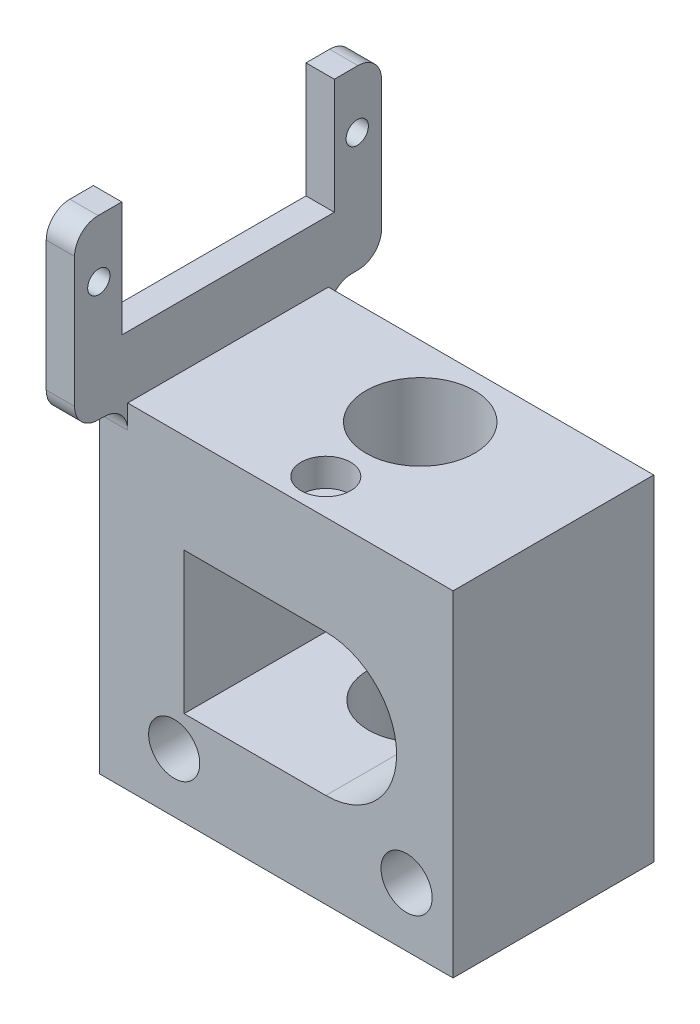
SolidWorks part; units mm, degrees
ref_plane "Front Plane" through (0, 0, 0) normal (0, 0, 1) x (1, 0, 0)
ref_plane "Top Plane" through (0, 0, 0) normal (0, 1, 0) x (1, 0, 0)
ref_plane "Right Plane" through (0, 0, 0) normal (1, 0, 0) x (0, 0, -1)
sketch "Sketch2" plane through (0, 0, 0) normal (0, 0, 1) x (1, 0, 0)
  line L1 (0, 0) -> (35, 0)
  line L2 (0, 0) -> (0, 36.068)
  line L3 (0, 36.068) -> (35, 36.068)
  line L4 (35, 0) -> (35, 36.068)
  dimension "D1" = 36.068
  dimension "D2" = 35
extrude "Boss-Extrude1" add sketch "Sketch2" along normal blind 21.59
hole_wizard "M5 Clearance Hole1" positions "Sketch3" profile "Sketch4" hole size "M5" standard "ANSI Metric" end condition through all
sketch "Sketch3" plane through (0, 0, 0) normal (0, 0, 1) x (1, 0, 0)
  line L0 (5, 6.35) -> (30, 6.35) construction
  line L2 (0, 0) -> (35, 0) construction
  point P0 (5, 6.35)
  point P2 (30, 6.35)
  point P12 (17.5, 0)
  point P13 (17.5, 6.35)
  dimension "D1" = 6.35
  dimension "D2" = 25
sketch "Sketch4" plane through (5, 6.35, 0) normal (1, 0, 0) x (0, 1, 0)
  line L0 (0, 0) -> (0, 21.59)
  line L1 (0, 21.59) -> (2.75, 21.59)
  line L2 (2.75, 21.59) -> (2.75, 0)
  line L5 (2.75, 0) -> (0, 0)
  line L11 (0, -6.35) -> (0, 107.95) construction
  dimension "Thru Hole Dia." = 5.5
  dimension "Thru Hole Depth" = 21.59
sketch "Sketch13" plane through (0, 0, 21.59) normal (0, 0, 1) x (1, 0, 0)
  line L1 (6.07, 25.4) -> (28.93, 25.4)
  line L2 (6.07, 25.4) -> (6.07, 10.16)
  line L3 (6.07, 10.16) -> (28.93, 10.16)
  line L4 (28.93, 25.4) -> (28.93, 10.16)
  line L5 (35, 36.068) -> (0, 36.068) construction
  line L7 (0, 0) -> (35, 0) construction
  point P6 (17.5, 36.068)
  point P7 (17.5, 25.4)
  dimension "D1" = 10.16
  dimension "D2" = 15.24
  dimension "D3" = 22.86
extrude "Cut-Extrude3" cut sketch "Sketch13" against normal through all
sketch "Sketch5" plane through (0, 36.068, 0) normal (0, 1, 0) x (1, 0, 0)
  line L0 (35, 0) -> (0, 0) construction
  circle A0 centre (17.5, -7.62) radius 5.842
  point P6 (17.5, 0)
  dimension "D1" = 11.684
  dimension "D2" = 7.62
extrude "Cut-Extrude1" cut sketch "Sketch5" against normal up to next
sketch "Sketch7" plane through (0, 0, 0) normal (-1, 0, 0) x (0, 0, 1)
  line L0 (21.59, 36.068) -> (0, 36.068) construction
  line L5 (-5.715, 36.068) -> (27.305, 36.068)
  line L6 (-5.715, 36.068) -> (-5.715, 55.118)
  line L7 (-5.715, 55.118) -> (27.305, 55.118)
  line L8 (27.305, 36.068) -> (27.305, 55.118)
  line L9 (21.59, 0) -> (0, 0) construction
  line L10 (-3.1039, 48.9204) -> (24.6939, 48.9204) construction
  line L12 (0, 36.068) -> (21.59, 36.068)
  line L13 (0, 36.068) -> (0, 0)
  line L14 (0, 0) -> (21.59, 0)
  line L15 (21.59, 36.068) -> (21.59, 0)
  line L16 (-0.635, 55.118) -> (22.225, 55.118)
  line L17 (-0.635, 55.118) -> (-0.635, 42.7228)
  line L18 (-0.635, 42.7228) -> (22.225, 42.7228)
  line L19 (22.225, 55.118) -> (22.225, 42.7228)
  point P7 (10.795, 55.118)
  point P10 (10.795, 0)
  point P15 (10.795, 48.9204)
  point P16 (10.795, 36.068)
  point P26 (10.795, 42.7228)
  point P28 (22.225, 48.9204)
  dimension "D1" = 33.02
  dimension "D2" = 19.05
  dimension "D3" = 27.7978
  dimension "D4" = 12.3952
  dimension "D5" = 22.86
extrude "Boss-Extrude2" add sketch "Sketch7" along normal blind 3.048
hole_wizard "M2 Clearance Hole1" positions "Sketch9" profile "Sketch10" hole size "M2" standard "ANSI Metric" end condition through all
sketch "Sketch9" plane through (-3.048, 0, 0) normal (-1, 0, 0) x (0, 0, 1)
  point P0 (-3.1039, 48.9204)
  point P3 (24.6939, 48.9204)
sketch "Sketch10" plane through (-3.048, 48.9204, -3.1039) normal (0, 1, 0) x (0, 0, 1)
  line L0 (0, 0) -> (0, 38.048)
  line L1 (0, 38.048) -> (1.2, 38.048)
  line L2 (1.2, 38.048) -> (1.2, 0)
  line L5 (1.2, 0) -> (0, 0)
  line L11 (0, -6.35) -> (0, 107.95) construction
  dimension "Thru Hole Dia." = 2.4
  dimension "Thru Hole Depth" = 38.048
fillet "Fillet2" radius 2.54 6 edges at (-1.524, 36.068, -5.715) (-1.524, 55.118, -5.715) (-1.524, 55.118, 27.305) (-1.524, 36.068, 27.305) (-1.524, 36.068, 0) (-1.524, 36.068, 21.59)
sketch "Sketch11" plane through (0, 36.068, 0) normal (0, 1, 0) x (1, 0, 0)
  line L1 (35, -21.59) -> (0, -21.59) construction
  circle A0 centre (17.5, -17.78) radius 2.667
  point P5 (17.5, -21.59)
  dimension "D1" = 5.334
  dimension "D3" = 3.81
extrude "Cut-Extrude2" cut sketch "Sketch11" against normal blind 3
sketch "Sketch14" plane through (0, 10.16, 0) normal (0, 1, 0) x (1, 0, 0)
  circle A0 centre (17.5, -7.62) radius 5.842 construction
  circle A1 centre (17.5, -7.62) radius 5.842
  circle A2 centre (17.5, -7.62) radius 5.588
  dimension "D1" = 0.254
extrude "Cut-Extrude4" cut sketch "Sketch14" against normal through all contours A2
fillet "Fillet3" radius 7.62 4 edges at (28.93, 17.78, 0) (28.93, 25.4, 10.795) (28.93, 10.16, 10.795) (28.93, 17.78, 21.59)
equation "\"press fit\"= 0.25mm"
equation "\"wall thick\"= 2mm"
equation "\"marker diamiter\"= 0.44"
equation "\"D1@Sketch5\"=\"marker diamiter\"+2*\"press fit\""
equation "\"D1@Boss-Extrude2\"=\"wall thick\"*1.5"
equation "\"D5@Sketch7\"=0.8858+\"press fit\""
equation "\"pin diamiter\"= 5mm"
equation "\"D1@Sketch11\"=\"pin diamiter\"+\"press fit\""
